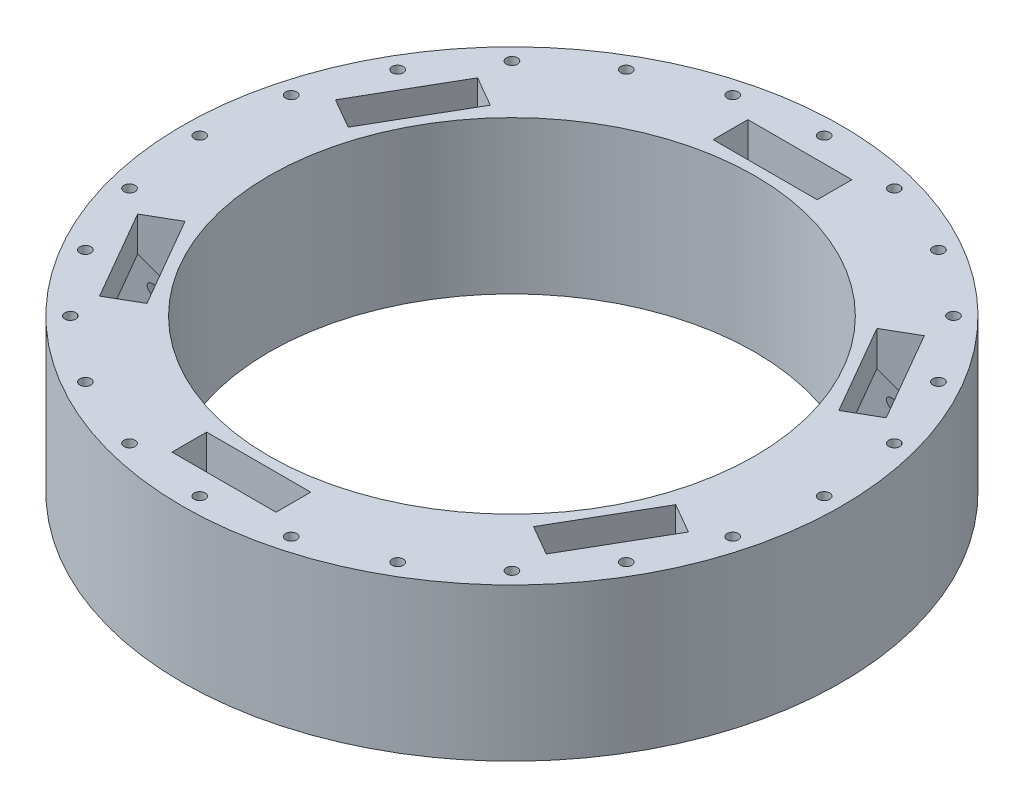
SolidWorks part; units mm, degrees
material "ABS"
ref_plane "Front Plane" through (0, 0, 0) normal (0, 0, 1) x (1, 0, 0)
ref_plane "Top Plane" through (0, 0, 0) normal (0, 1, 0) x (1, 0, 0)
ref_plane "Right Plane" through (0, 0, 0) normal (1, 0, 0) x (0, 0, -1)
sketch "Sketch1" plane through (0, 0, 0) normal (0, 1, 0) x (1, 0, 0)
  circle A0 centre (0, 0) radius 95
  circle A1 centre (0, 0) radius 70
  dimension "D1" = 190
  dimension "D2" = 140
extrude "Boss-Extrude1" add sketch "Sketch1" along normal blind 44
ref_axis "Axis1" through (0, 44, 0) along (0, -1, 0)
ref_plane "Plane1" through (0, 0, 0) normal (-0.5, 0, 0.866) x (0, -1, 0)
sketch "Sketch7" plane through (0, 0, 0) normal (-0.5, 0, 0.866) x (0, -1, 0)
  line L0 (-44, 78) -> (-59.5063, 78) construction
  line L1 (-44, 83) -> (-34, 83)
  line L2 (-44, 83) -> (-44, 73)
  line L3 (-44, 73) -> (-34, 73)
  line L4 (-34, 83) -> (-29, 78)
  line L5 (-44, 83) -> (-34, 73) construction
  line L6 (-44, 73) -> (-34, 83) construction
  line L7 (-29, 78) -> (-34, 73)
  line L8 (-44, 95) -> (-44, -95) construction
  line L9 (0, 78) -> (18.597, 78) construction
  line L10 (-10, 83) -> (0, 83)
  line L11 (-10, 83) -> (-15, 78)
  line L12 (-10, 73) -> (0, 73)
  line L13 (0, 83) -> (0, 73)
  line L14 (-10, 83) -> (0, 73) construction
  line L15 (-10, 73) -> (0, 83) construction
  line L16 (-15, 78) -> (-10, 73)
  line L17 (0, 95) -> (-44, 95) construction
  line L18 (0, -95) -> (0, 95) construction
  point P0 (-39, 78)
  point P8 (-5, 78)
  dimension "D1" = 10
  dimension "D2" = 10
  dimension "D3" = 12
  dimension "D4" = 10
  dimension "D5" = 10
  dimension "D6" = 12
extrude "Cut-Extrude3" cut sketch "Sketch7" against normal blind 15 and the other way blind 15
pattern_circular "CirPattern2" count 6 over 360 about axis through (0, 44, 0) along (0, -1, 0) of "Cut-Extrude3"
hole_wizard "M3 Clearance Hole1" positions "Sketch8" profile "Sketch9" hole size "M3" standard "ANSI Metric" end condition through all
sketch "Sketch8" plane through (0, 44, 0) normal (0, 1, 0) x (1, 0, 0)
  line L1 (0, 0) -> (119.0136, -68.7125) construction
  line L3 (0, 0) -> (147.5995, 0) construction
  line L5 (60.05, -51.9904) -> (75.05, -26.0096) construction
  line L6 (64.3801, -54.4904) -> (55.7199, -49.4904) construction
  line L7 (79.3801, -28.5096) -> (70.7199, -23.5096) construction
  point P0 (62.55, -47.6603)
  point P19 (72.55, -30.3397)
  point P25 (-10, -78)
  point P26 (10, -78)
  point P27 (-72.55, -30.3397)
  point P28 (-62.55, -47.6603)
  point P29 (-62.55, 47.6603)
  point P30 (-72.55, 30.3397)
  point P31 (10, 78)
  point P32 (-10, 78)
  point P33 (72.55, 30.3397)
  point P34 (62.55, 47.6603)
  point P35 (0, 0)
  dimension "D1" = 30
  dimension "D2" = 20
  dimension "D3" = 6
sketch "Sketch9" plane through (62.55, 44, 47.6603) normal (1, 0, 0) x (0, 0, 1)
  line L0 (0, 0) -> (0, 44)
  line L1 (0, 44) -> (1.6, 44)
  line L2 (1.6, 44) -> (1.6, 0)
  line L5 (1.6, 0) -> (0, 0)
  line L11 (0, -6.35) -> (0, 107.95) construction
  dimension "Thru Hole Dia." = 3.2
  dimension "Thru Hole Depth" = 44
hole_wizard "M3 Clearance Hole2" positions "Sketch14" profile "Sketch13" hole size "M3" standard "ANSI Metric" end condition through all
sketch "Sketch14" plane through (0, 44, 0) normal (0, 1, 0) x (1, 0, 0)
  line L0 (0, 0) -> (0, 95) construction
  circle A0 centre (0, 0) radius 95 construction
  point P0 (0, 90)
  point P19 (23.2937, 86.9333)
  point P20 (45, 77.9423)
  point P21 (63.6396, 63.6396)
  point P22 (77.9423, 45)
  point P23 (86.9333, 23.2937)
  point P24 (90, 0)
  point P25 (86.9333, -23.2937)
  point P26 (77.9423, -45)
  point P27 (63.6396, -63.6396)
  point P28 (45, -77.9423)
  point P29 (23.2937, -86.9333)
  point P30 (0, -90)
  point P31 (-23.2937, -86.9333)
  point P32 (-45, -77.9423)
  point P33 (-63.6396, -63.6396)
  point P34 (-77.9423, -45)
  point P35 (-86.9333, -23.2937)
  point P36 (-90, 0)
  point P37 (-86.9333, 23.2937)
  point P38 (-77.9423, 45)
  point P39 (-63.6396, 63.6396)
  point P40 (-45, 77.9423)
  point P41 (-23.2937, 86.9333)
  point P42 (0, 0)
  dimension "D1" = 90
  dimension "D2" = 24
sketch "Sketch13" plane through (0, 44, -90) normal (1, 0, 0) x (0, 0, 1)
  line L0 (0, 0) -> (0, 44)
  line L1 (0, 44) -> (1.6, 44)
  line L2 (1.6, 44) -> (1.6, 0)
  line L5 (1.6, 0) -> (0, 0)
  line L11 (0, -6.35) -> (0, 107.95) construction
  dimension "Thru Hole Dia." = 3.2
  dimension "Thru Hole Depth" = 44
